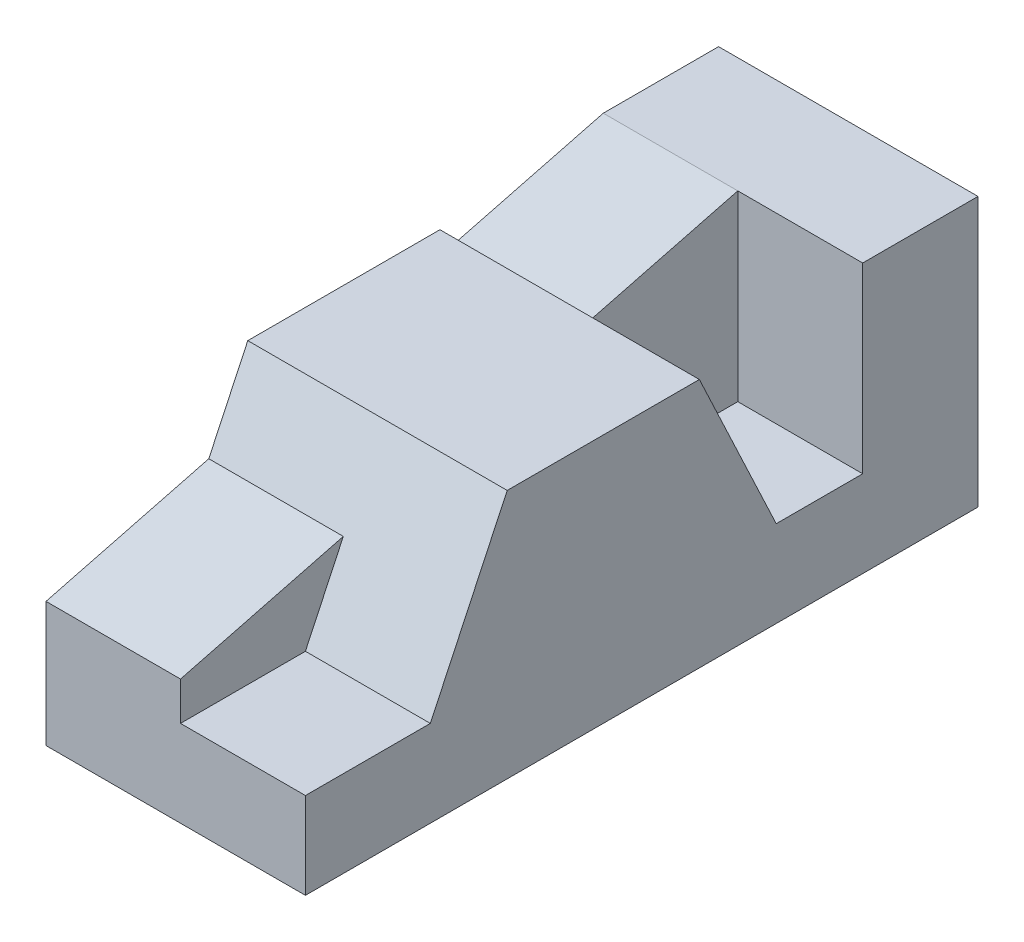
SolidWorks part; units mm, degrees
ref_plane "Front Plane" through (0, 0, 0) normal (0, 0, 1) x (1, 0, 0)
ref_plane "Top Plane" through (0, 0, 0) normal (0, 1, 0) x (1, 0, 0)
ref_plane "Right Plane" through (0, 0, 0) normal (1, 0, 0) x (0, 0, -1)
sketch "Sketch1" plane through (0, 0, 0) normal (1, 0, 0) x (0, 0, -1)
  line L0 (-350, 90) -> (-350, 0)
  line L1 (-350, 0) -> (350, 0)
  line L2 (350, 0) -> (350, 280)
  line L3 (350, 280) -> (230, 280)
  line L4 (230, 280) -> (230, 90)
  line L5 (230, 90) -> (140, 90)
  line L6 (140, 90) -> (60, 260)
  line L7 (60, 260) -> (-140, 260)
  line L8 (-140, 260) -> (-220, 90)
  line L9 (-220, 90) -> (-350, 90)
  point P12 (0, 0)
  dimension "D1" = 90
  dimension "D2" = 280
  dimension "D3" = 700
  dimension "D4" = 120
  dimension "D5" = 360
  dimension "D6" = 200
  dimension "D7" = 570
  dimension "D8" = 260
extrude "Boss-Extrude1" add sketch "Sketch1" along normal blind 135 and the other way blind 135
sketch "Sketch3" plane through (-135, 0, 0) normal (-1, 0, 0) x (0, 0, 1)
  line L0 (350, 90) -> (350, 130)
  line L1 (350, 130) -> (180.5543, 173.8222)
  line L2 (-230, 280) -> (-230, 90)
  line L3 (-230, 90) -> (-140, 90)
  line L4 (-140, 90) -> (-70.0542, 238.6347)
  line L5 (350, 90) -> (220, 90)
  line L6 (220, 90) -> (350, 90) construction
  line L7 (220, 90) -> (180.5543, 173.8222)
  line L9 (-70.0542, 238.6347) -> (-230, 280)
  dimension "D1" = 40
extrude "Boss-Extrude2" add sketch "Sketch3" against normal blind 140
